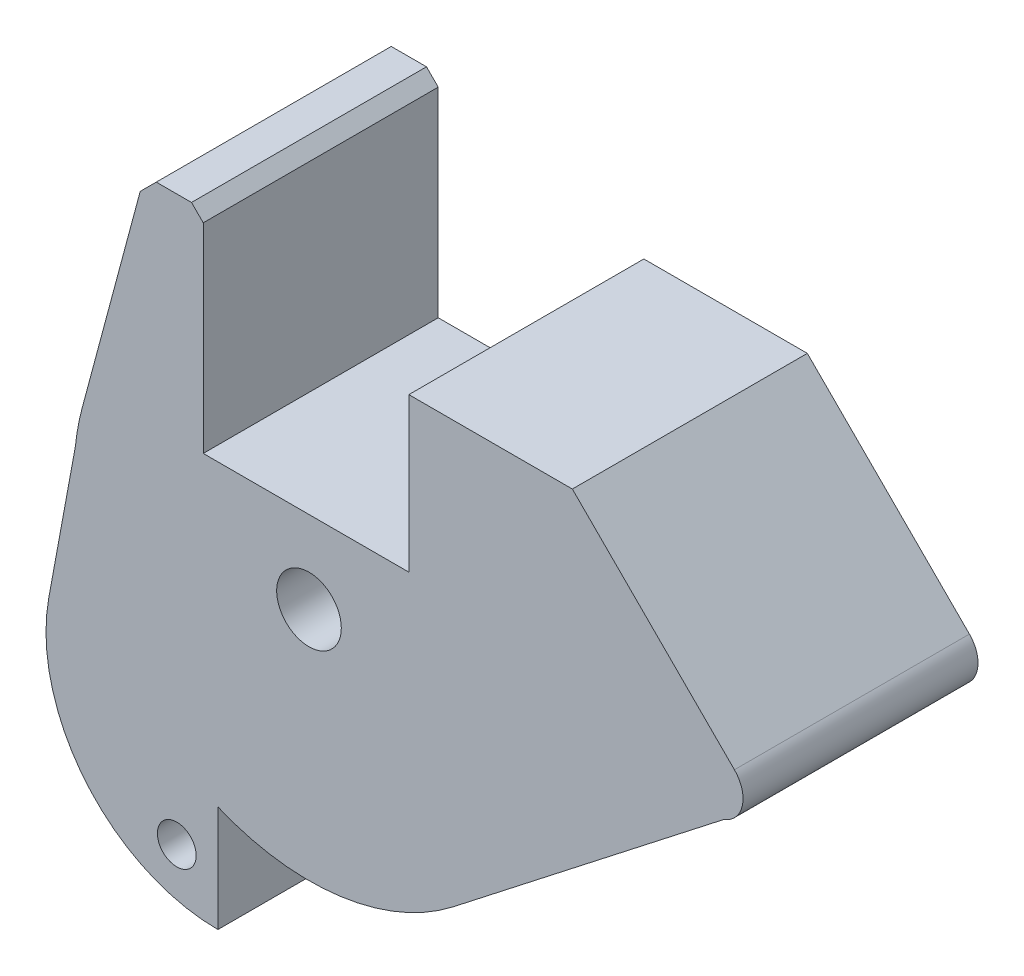
SolidWorks part; units mm, degrees
material "POM 乙缩醛共聚物"
ref_plane "前视基准面" through (0, 0, 0) normal (0, 0, 1) x (1, 0, 0)
ref_plane "上视基准面" through (0, 0, 0) normal (0, 1, 0) x (1, 0, 0)
ref_plane "右视基准面" through (0, 0, 0) normal (1, 0, 0) x (0, 0, -1)
sketch "草图1" plane through (0, 0, 0) normal (0, 0, 1) x (1, 0, 0)
  line L0 (0, 0) -> (0, 18)
  line L1 (0, 18) -> (-5, 18)
  line L4 (44.3198, -4.8198) -> (49.3198, -4.8198)
  line L5 (49.3198, -4.8198) -> (17.5, 27)
  line L6 (17.5, 27) -> (17.5, 0)
  line L7 (17.5, 0) -> (0, 0)
  line L8 (-5, 18) -> (-10.3122, -1.8253)
  line L9 (21.291, -22.7692) -> (44.3198, -4.8198)
  circle A1 centre (9, -7) radius 2.75
  arc A2 (-10.3122, -1.8253) -> (21.291, -22.7692) centre (9, -7) ccw
  dimension "D10" = 5.5
  dimension "D11" = 5
  dimension "D1" = 45
  dimension "D2" = 18
  dimension "D3" = 17.5
  dimension "D4" = 27
  dimension "D5" = 7
  dimension "D6" = 9
  dimension "D7" = 5
  dimension "D8" = 75
  dimension "D9" = 45
extrude "凸台-拉伸1" add sketch "草图1" along normal blind 20
chamfer "倒角1" distance 1 angle 45 2 edges at (-5, 18, 10) (0, 18, 10)
fillet "圆角1" radius 2.5 2 edges at (17.5, 27, 10) (49.3198, -4.8198, 10)
sketch "草图2" plane through (0, 0, 20) normal (0, 0, 1) x (1, 0, 0)
  line L0 (17.5, 20.9645) -> (17.5, 0) construction
  line L1 (17.5, 13.0846) -> (45.7398, 13.0846)
  line L2 (17.5, 13.0846) -> (17.5, 25.3005)
  line L3 (17.5, 25.3005) -> (45.7398, 25.3005)
  line L4 (45.7398, 13.0846) -> (45.7398, 25.3005)
extrude "切除-拉伸1" cut sketch "草图2" against normal through all
sketch "草图3" plane through (0, 0, 20) normal (0, 0, 1) x (1, 0, 0)
  line L0 (-10.3122, -1.8253) -> (-13.1427, -17.1901)
  line L1 (10.2419, -31.3813) -> (21.291, -22.7692)
  line L2 (21.291, -22.7692) -> (44.3198, -4.8198) construction
  line L13 (31.4154, 13.0846) -> (17.5, 13.0846)
  line L14 (17.5, 13.0846) -> (17.5, 0)
  line L15 (17.5, 0) -> (0, 0)
  line L16 (0, 0) -> (0, 17)
  line L17 (0, 17) -> (-1, 18)
  line L18 (-1, 18) -> (-4, 18)
  line L19 (-4, 18) -> (-5.366, 16.634)
  line L20 (-5.366, 16.634) -> (-10.3122, -1.8253)
  line L21 (21.291, -22.7692) -> (44.3198, -4.8198)
  line L22 (45.2108, -0.7108) -> (31.4154, 13.0846)
  arc A0 (-13.1427, -17.1901) -> (10.2419, -31.3813) centre (1.2469, -19.841) ccw
  arc A3 (-10.3122, -1.8253) -> (21.291, -22.7692) centre (9, -7) ccw
  arc A4 (44.3198, -4.8198) -> (45.2108, -0.7108) centre (43.4431, -2.4786) ccw
  arc A5 (-10.3122, -1.8253) -> (21.291, -22.7692) centre (9, -7) ccw
  arc M22 (-10.3122, -1.8253) -> (21.291, -22.7692) centre (9, -7) ccw
  dimension "D2" = 15
  dimension "D1" = 0
extrude "凸台-拉伸2" add sketch "草图3" against normal blind 10 contours L0 A0 L1 M22
sketch "草图4" plane through (0, 0, 10) normal (0, 0, -1) x (-1, 0, 0)
  line L0 (-1.2469, -34.4727) -> (-1.2469, -25.429)
  line L1 (-10.2419, -31.3813) -> (-21.291, -22.7692) construction
  line L2 (-10.2419, -31.3813) -> (-21.291, -22.7692)
  arc A0 (-10.2419, -31.3813) -> (13.1427, -17.1901) centre (-1.2469, -19.841) ccw construction
  arc A1 (-21.291, -22.7692) -> (10.3122, -1.8253) centre (-9, -7) ccw construction
  arc A2 (-21.291, -22.7692) -> (-1.2469, -25.429) centre (-9, -7) ccw
  arc A3 (-10.2419, -31.3813) -> (-1.2469, -34.4727) centre (-1.2469, -19.841) ccw
  circle A4 centre (2.2531, -29.9509) radius 1.65
  dimension "D1" = 3.3
  dimension "D2" = 3.5
extrude "切除-拉伸2" cut sketch "草图4" against normal blind 10
